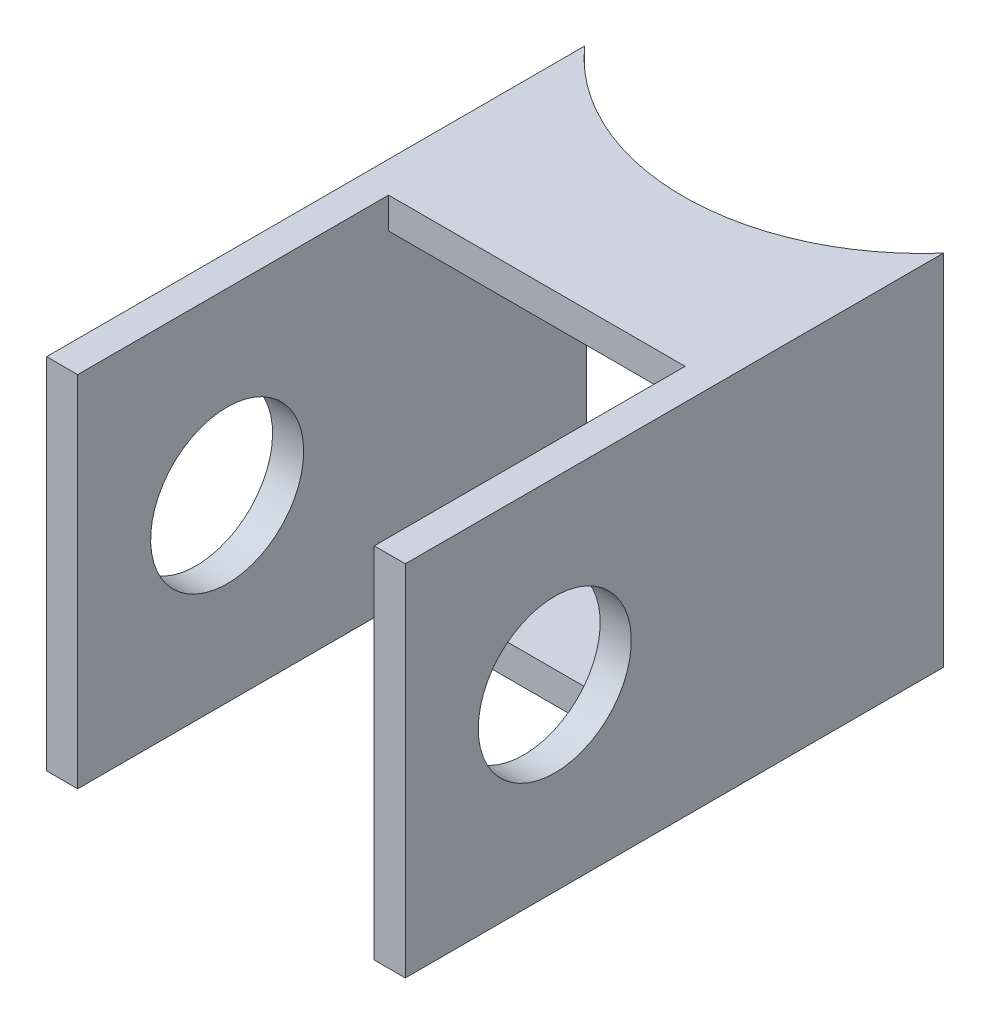
SolidWorks part; units mm, degrees
material "AISI 4130 Steel, annealed at 865C"
ref_plane "Front Plane" through (0, 0, 0) normal (0, 0, 1) x (1, 0, 0)
ref_plane "Top Plane" through (0, 0, 0) normal (0, 1, 0) x (1, 0, 0)
ref_plane "Right Plane" through (0, 0, 0) normal (1, 0, 0) x (0, 0, -1)
sketch "Sketch1" plane through (0, 0, 0) normal (0, 0, 1) x (1, 0, 0)
  line L1 (-9.525, 9.525) -> (9.525, 9.525)
  line L2 (-9.525, 9.525) -> (-9.525, -9.525)
  line L3 (-9.525, -9.525) -> (9.525, -9.525)
  line L4 (9.525, 9.525) -> (9.525, -9.525)
  line L5 (-9.525, 9.525) -> (9.525, -9.525) construction
  line L6 (-9.525, -9.525) -> (9.525, 9.525) construction
  line L7 (-7.874, 7.874) -> (7.874, 7.874)
  line L8 (-7.874, 7.874) -> (-7.874, -7.874)
  line L9 (-7.874, -7.874) -> (7.874, -7.874)
  line L10 (7.874, 7.874) -> (7.874, -7.874)
  line L11 (-7.874, 7.874) -> (7.874, -7.874) construction
  line L12 (-7.874, -7.874) -> (7.874, 7.874) construction
  point P0 (0, 0)
  point P6 (0, 0)
  dimension "D1" = 19.05
  dimension "D2" = 1.651
extrude "Boss-Extrude1" add sketch "Sketch1" along normal blind 28.575
sketch "Sketch5" plane through (0, 9.525, 0) normal (0, 1, 0) x (1, 0, 0)
  line L0 (0, -1000) -> (0, 49000) construction
  circle A0 centre (0, 8.4003) radius 12.7
  dimension "D1" = 25.4
extrude "Cut-Extrude5" cut sketch "Sketch5" against normal through all both and the other way through all
sketch "Sketch3" plane through (9.525, 0, 0) normal (1, 0, 0) x (0, 0, -1)
  line L0 (-28.575, -9.525) -> (0, -9.525) construction
  line L1 (-28.575, 9.525) -> (-20.6375, 9.525) construction
  line L2 (-28.575, 9.525) -> (-28.575, -9.525) construction
  line L3 (-28.575, -9.525) -> (-20.6375, -9.525) construction
  line L4 (-20.6375, 9.525) -> (-20.6375, -9.525) construction
  line L5 (-24.6062, -9.525) -> (-24.6062, 9.525) construction
  line L6 (-28.575, 0) -> (-20.6375, 0) construction
  circle A0 centre (-20.6375, 0) radius 4.064
  point P168 (-24.6062, 0)
  dimension "D1" = 8.128
  dimension "D2" = 7.9375
extrude "Cut-Extrude2" cut sketch "Sketch3" against normal through all both and the other way through all
sketch "Sketch4" plane through (0, -9.525, 0) normal (0, -1, 0) x (1, 0, 0)
  line L1 (-7.874, 28.575) -> (7.874, 28.575)
  line L2 (-7.874, 28.575) -> (-7.874, 12.065)
  line L3 (-7.874, 12.065) -> (7.874, 12.065)
  line L4 (7.874, 28.575) -> (7.874, 12.065)
  line L5 (0, 12.065) -> (0, 28.575) construction
  line L6 (-7.874, 20.32) -> (7.874, 20.32) construction
  line L7 (7.874, 24.7015) -> (7.874, 16.5735) construction
  point P96 (0, 20.32)
  dimension "D1" = 16.51
extrude "Cut-Extrude4" cut sketch "Sketch4" against normal through all both and the other way through all
fillet "Fillet2" [suppressed] radius 6.35
ref_axis "Axis2" through (-9.525, 0, 20.6375) along (1, 0, 0)
ref_point "Point2"
ref_axis "Axis3" through (0, 0, 0) along (0, 0, 1)
sketch "Sketch6" plane through (0, 9.525, 0) normal (0, 1, 0) x (1, 0, 0)
  circle A2 centre (0, 5.2253) radius 9.525
  arc A3 (-9.525, 0) -> (9.525, 0) centre (0, 8.4003) ccw construction
  dimension "D1" = 19.05
  dimension "D2" = 5.2253
